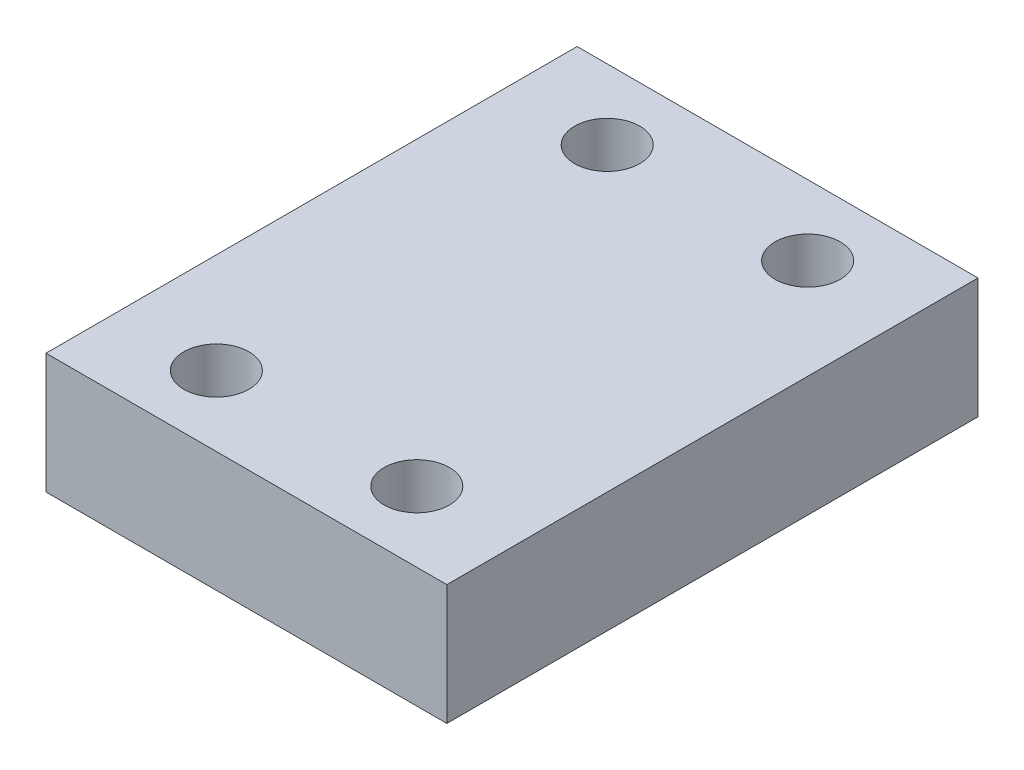
SolidWorks part; units mm, degrees
ref_plane "Front Plane" through (0, 0, 0) normal (0, 0, 1) x (1, 0, 0)
ref_plane "Top Plane" through (0, 0, 0) normal (0, 1, 0) x (1, 0, 0)
ref_plane "Right Plane" through (0, 0, 0) normal (1, 0, 0) x (0, 0, -1)
sketch "Sketch1" plane through (0, 0, 0) normal (0, 1, 0) x (1, 0, 0)
  line L0 (13.8021, -16.7414) -> (-19.1979, -16.7414) construction
  line L6 (-17.5215, -33.2414) -> (22.4785, -33.2414)
  line L7 (13.8021, 3.2586) -> (-8.845, 3.2586) construction
  line L8 (13.8021, 3.2586) -> (13.8021, -16.7414) construction
  line L9 (13.8021, -16.7414) -> (-8.845, -16.7414) construction
  line L10 (-8.845, 3.2586) -> (-8.845, -16.7414) construction
  line L11 (-8.845, 3.2586) -> (13.8021, -16.7414) construction
  line L12 (-8.845, -16.7414) -> (13.8021, 3.2586) construction
  line L13 (-17.5215, -33.2414) -> (-17.5215, 19.7586)
  line L14 (-17.5215, 19.7586) -> (22.4785, 19.7586)
  line L15 (22.4785, -33.2414) -> (22.4785, 19.7586)
  line L16 (-17.5215, -33.2414) -> (22.4785, 19.7586) construction
  line L17 (-17.5215, 19.7586) -> (22.4785, -33.2414) construction
  point P0 (0, 0)
  point P1 (2.4785, -6.7414)
  dimension "D1" = 53
  dimension "D2" = 40
extrude "Boss-Extrude1" add sketch "Sketch1" along normal blind 12
sketch "Sketch2" plane through (0, 0, 0) normal (0, -1, 0) x (1, 0, 0)
  line L0 (2.4785, -19.7586) -> (2.4785, 33.2414) construction
  line L1 (22.4785, -19.7586) -> (-17.5215, -19.7586) construction
  line L2 (-17.5215, 33.2414) -> (22.4785, 33.2414) construction
  circle A0 centre (2.4785, 6.7414) radius 8
  dimension "D1" = 16
extrude "Cut-Extrude1" cut sketch "Sketch2" against normal blind 6
sketch "Sketch4" plane through (0, 6, 0) normal (0, -1, 0) x (1, 0, 0)
  circle A0 centre (2.4785, 6.7414) radius 4.25
  dimension "D1" = 8.5
extrude "Cut-Extrude2" cut sketch "Sketch4" against normal blind 1.5
sketch "Sketch5" plane through (0, 12, 0) normal (0, 1, 0) x (1, 0, 0)
  line L0 (-17.5215, -26.2414) -> (22.4785, -26.2414) construction
  line L1 (-17.5215, 19.7586) -> (-17.5215, -33.2414) construction
  line L2 (22.4785, -33.2414) -> (22.4785, 19.7586) construction
  line L3 (-17.5215, 12.7586) -> (22.4785, 12.7586) construction
  line L4 (-17.5215, -33.2414) -> (22.4785, -33.2414) construction
  line L5 (22.4785, 19.7586) -> (-17.5215, 19.7586) construction
  circle A0 centre (-7.5215, -26.2414) radius 3.25
  circle A1 centre (12.4785, -26.2414) radius 3.25
  circle A2 centre (-7.5215, 12.7586) radius 3.25
  circle A3 centre (12.4785, 12.7586) radius 3.25
  dimension "D3" = 6.5
  dimension "D4" = 6.5
  dimension "D5" = 6.5
  dimension "D6" = 6.5
  dimension "D1" = 7
  dimension "D2" = 7
  dimension "D7" = 10
  dimension "D8" = 10
  dimension "D9" = 10
  dimension "D10" = 10
extrude "Cut-Extrude3" cut sketch "Sketch5" against normal up to next
sketch "Sketch6" plane through (0, 0, 0) normal (0, 1, 0) x (1, 0, 0)
  circle A0 centre (12.4785, 12.7586) radius 3.25 construction
  circle A1 centre (-7.5215, 12.7586) radius 3.25 construction
  circle A2 centre (2.4785, -6.7414) radius 4.25 construction
  circle A3 centre (2.4785, -6.7414) radius 8 construction
  circle A4 centre (12.4785, -26.2414) radius 3.25 construction
  circle A5 centre (-7.5215, -26.2414) radius 3.25 construction
  circle A6 centre (12.4785, 12.7586) radius 3.25
  circle A7 centre (-7.5215, 12.7586) radius 3.25
  circle A8 centre (2.4785, -6.7414) radius 4.25
  circle A9 centre (2.4785, -6.7414) radius 8
  circle A10 centre (12.4785, -26.2414) radius 3.25
  circle A11 centre (-7.5215, -26.2414) radius 3.25
